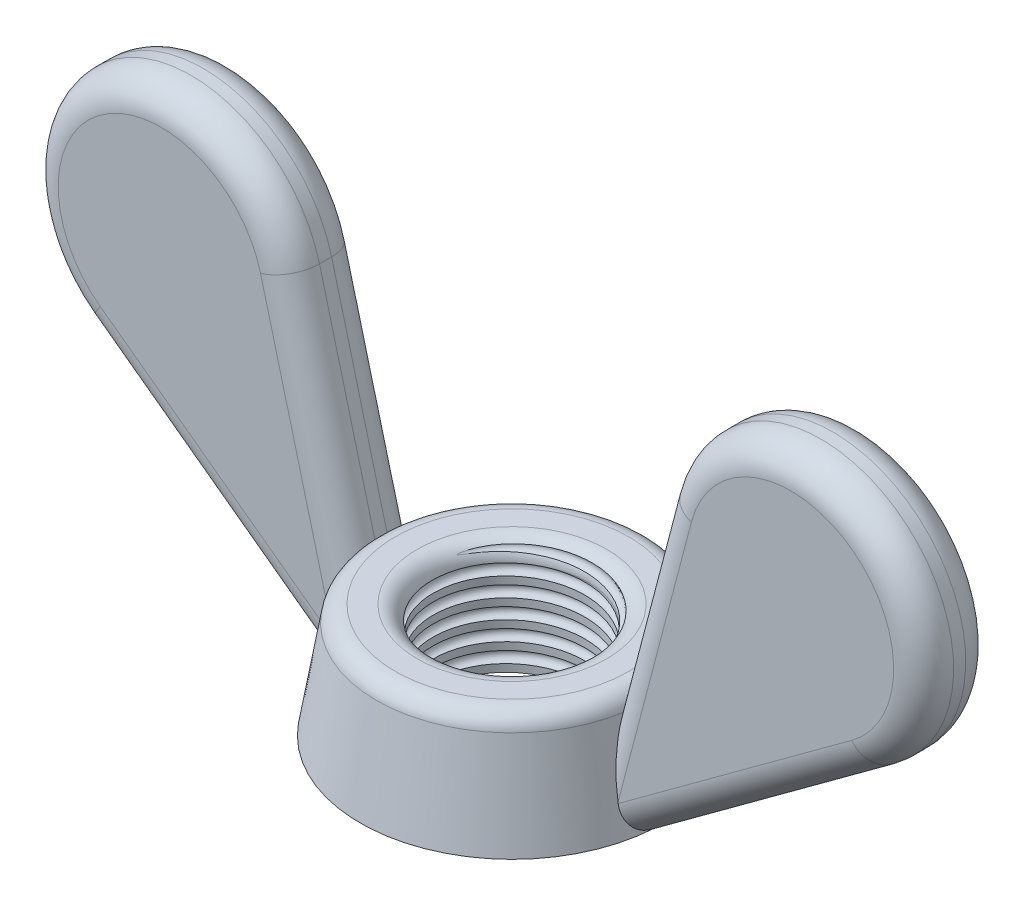
SolidWorks part; units mm, degrees
ref_plane "Front Plane" through (0, 0, 0) normal (0, 0, 1) x (1, 0, 0)
ref_plane "Top Plane" through (0, 0, 0) normal (0, 1, 0) x (1, 0, 0)
ref_plane "Right Plane" through (0, 0, 0) normal (1, 0, 0) x (0, 0, -1)
sketch "Sketch2" plane through (0, 0, 0) normal (0, 0, 1) x (1, 0, 0)
  line L0 (0, 3) -> (0, 0)
  line L1 (0, 0) -> (4, 0)
  line L2 (0, 3) -> (3.5, 3)
  line L3 (3.5, 3) -> (4, 0)
  dimension "D1" = 3
  dimension "D2" = 4
  dimension "D3" = 3.5
revolve "Revolve1" add sketch "Sketch2" angle 360 about L0
sketch "Sketch3" plane through (0, 0, 0) normal (0, 0, 1) x (1, 0, 0)
  line L0 (0, 11) -> (0, -4.103) construction
  line L1 (0, 11) -> (11.8, 11) construction
  line L2 (11.8, 11) -> (11.8, -0.2232) construction
  line L3 (-4, 0) -> (4, 0) construction
  line L4 (4.9147, 8.3887) -> (3.3885, 2.5754)
  line L5 (10.3716, 4.6789) -> (4, 0)
  line L6 (4, 0) -> (3.8748, 0)
  line L7 (3.8748, 0) -> (3.3885, 2.5754)
  arc A0 (10.3716, 4.6789) -> (4.9147, 8.3887) centre (8.3, 7.5) ccw
  dimension "D3" = 7
  dimension "D1" = 11.8
  dimension "D2" = 11
extrude "Boss-Extrude1" add sketch "Sketch3" along normal mid plane 1.9
mirror "Mirror1" about plane through (0, 0, 0) normal (1, 0, 0) of "Boss-Extrude1"
fillet "Fillet1" radius 0.79 12 edges at (7.1858, 2.3395, -0.95) (4.1678, 5.5436, -0.95) (7.1858, 2.3395, 0.95) (4.1678, 5.5436, 0.95) (-7.1858, 2.3395, -0.95) (-4.1678, 5.5436, -0.95) (-7.1858, 2.3395, 0.95) (-4.1678, 5.5436, 0.95) (10.2678, 10.3945, -0.95) (10.2678, 10.3945, 0.95) (-10.2678, 10.3945, -0.95) (-10.2678, 10.3945, 0.95)
sketch "Sketch4" plane through (0, 0, 0) normal (0, 1, 0) x (1, 0, 0)
  circle A0 centre (0, 0) radius 2
  dimension "D1" = 4
extrude "Cut-Extrude1" cut sketch "Sketch4" against normal through all both and the other way through all
fillet "Fillet2" radius 0.5 3 edges at (2, 3, 0) (0, 3, -3.5) (0, 3, 3.5)
sketch "Sketch6" plane through (0, 0, 0) normal (0, -1, 0) x (1, 0, 0)
  circle A0 centre (0, 0) radius 2 construction
  circle A1 centre (0, 0) radius 2
curve "Helix/Spiral1" pitch 0.5 height 3.625 radius 2 centre (0, 0, 0) axis (0, 1, 0) start towards (-0.7071, 0, 0.7071)
sketch "Sketch7" plane through (0, 0, 0) normal (0, 0, 1) x (1, 0, 0)
  circle A0 centre (2, 0.1875) radius 0.15
  dimension "D1" = 0.3
sweep "Cut-Sweep1" cut profiles "Sketch7" path "Helix/Spiral1" align with end faces yes
